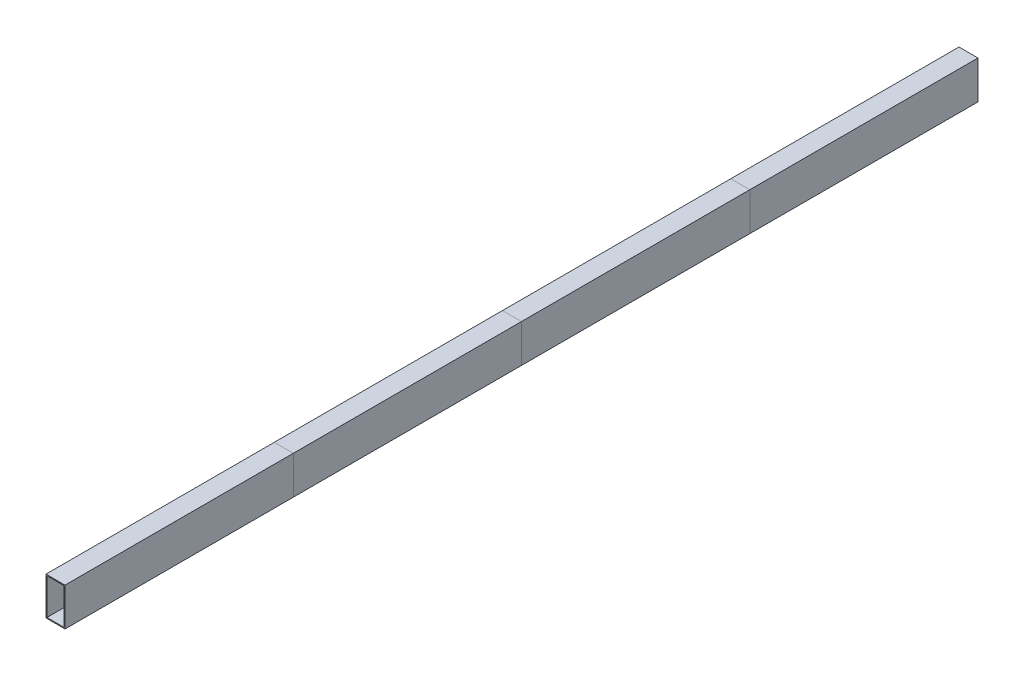
SolidWorks part; units mm, degrees
ref_plane "Спереди" through (0, 0, 0) normal (0, 0, 1) x (1, 0, 0)
ref_plane "Сверху" through (0, 0, 0) normal (0, 1, 0) x (1, 0, 0)
ref_plane "Справа" through (0, 0, 0) normal (1, 0, 0) x (0, 0, -1)
sketch "Эскиз1" plane through (0, 0, 0) normal (0, 0, 1) x (1, 0, 0)
  line L1 (-50, -100) -> (50, -100)
  line L2 (-50, -100) -> (-50, 100)
  line L3 (-50, 100) -> (50, 100)
  line L4 (50, -100) -> (50, 100)
  line L5 (-50, -100) -> (50, 100) construction
  line L6 (-50, 100) -> (50, -100) construction
  line L7 (-45, -95) -> (45, -95)
  line L8 (-45, -95) -> (-45, 95)
  line L9 (-45, 95) -> (45, 95)
  line L10 (45, -95) -> (45, 95)
  line L11 (-45, -95) -> (45, 95) construction
  line L12 (-45, 95) -> (45, -95) construction
  point P0 (0, 0)
  point P7 (0, 0)
  dimension "D1" = 100
  dimension "D2" = 200
  dimension "D3" = 90
  dimension "D4" = 190
extrude "Бобышка-Вытянуть1" add sketch "Эскиз1" along normal blind 1200
extrude "Бобышка-Вытянуть2" add sketch "Эскиз1<2>" along normal blind 1200 from surface separate body starting at face at (0, 0, 1200)
sketch "Эскиз1<2>" plane through (0, 0, 0) normal (0, 0, 1) x (1, 0, 0) same geometry as "Эскиз1"
extrude "Бобышка-Вытянуть3" add sketch "Эскиз1<3>" along normal blind 1200 from surface separate body starting at face at (0, 0, 2400)
sketch "Эскиз1<3>" plane through (0, 0, 0) normal (0, 0, 1) x (1, 0, 0) same geometry as "Эскиз1"
extrude "Бобышка-Вытянуть4" add sketch "Эскиз1<4>" along normal blind 1200 from surface separate body starting at face at (0, 0, 3600)
sketch "Эскиз1<4>" plane through (0, 0, 0) normal (0, 0, 1) x (1, 0, 0) same geometry as "Эскиз1"
ref_point "Точка1"
ref_point "Точка3"
